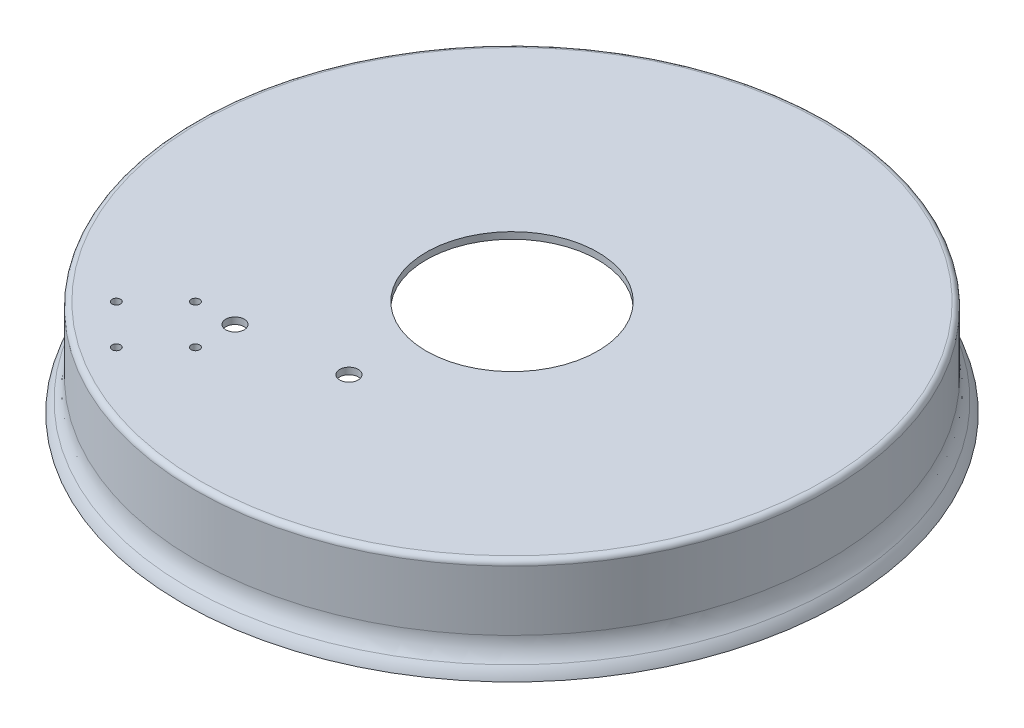
SolidWorks part; units mm, degrees
ref_plane "Front Plane" through (0, 0, 0) normal (0, 0, 1) x (1, 0, 0)
ref_plane "Top Plane" through (0, 0, 0) normal (0, 1, 0) x (1, 0, 0)
ref_plane "Right Plane" through (0, 0, 0) normal (1, 0, 0) x (0, 0, -1)
sketch "Sketch1" plane through (0, 0, 0) normal (0, 1, 0) x (1, 0, 0)
  circle A0 centre (0, 0) radius 120
  circle A1 centre (0, 0) radius 118
  dimension "D1" = 240
  dimension "D2" = 236
extrude "Boss-Extrude1" add sketch "Sketch1" along normal blind 32
sketch "Sketch2" plane through (0, 32, 0) normal (0, 1, 0) x (1, 0, 0)
  circle A0 centre (0, 0) radius 120
  circle A1 centre (0, 0) radius 32.5
  dimension "D1" = 65
  dimension "D2" = 240
extrude "Boss-Extrude2" add sketch "Sketch2" along normal blind 2.5
sketch "Sketch3" plane through (0, 34.5, 0) normal (0, 1, 0) x (1, 0, 0)
  circle A0 centre (-75, -75) radius 1.6
  circle A1 centre (-60, -60) radius 1.6
  circle A2 centre (-45, -75) radius 1.6
  circle A3 centre (-60, -90) radius 1.6
  dimension "D1" = 3.2
  dimension "D2" = 3.2
  dimension "D3" = 3.2
  dimension "D4" = 3.2
  dimension "D5" = 30
  dimension "D6" = 30
  dimension "D7" = 15
  dimension "D8" = 15
  dimension "D9" = 60
  dimension "D10" = 60
extrude "Cut-Extrude1" cut sketch "Sketch3" against normal up to surface (2.5 mm away) up to face at (0, 32, 32.5)
sketch "Sketch4" plane through (0, 34.5, 0) normal (0, 1, 0) x (1, 0, 0)
  circle A0 centre (-45, -60) radius 3.5
  circle A1 centre (-60, -60) radius 1.6 construction
  circle A2 centre (-45, -75) radius 1.6 construction
  dimension "D1" = 7
  dimension "D2" = 15
  dimension "D3" = 15
extrude "Cut-Extrude2" cut sketch "Sketch4" against normal up to surface (2.5 mm away) up to face at (-75, 32, 76.6)
fillet "Fillet1" radius 2 1 edges at (0, 34.5, 120)
sketch "Sketch5" plane through (0, 0, 0) normal (0, -1, 0) x (1, 0, 0)
  circle A0 centre (0, 0) radius 118
  circle A1 centre (0, 0) radius 125
  dimension "D1" = 250
  dimension "D2" = 236
extrude "Boss-Extrude3" add sketch "Sketch5" along normal blind 2
fillet "Fillet2" radius 12 1 edges at (0, 0, 120)
fillet "Fillet3" radius 12 1 edges at (0, 0, -125)
sketch "Sketch6" plane through (0, 34.5, 0) normal (0, 1, 0) x (1, 0, 0)
  circle A0 centre (-6.9162, -54.8774) radius 3.5
  point P2 (-6.9162, -54.8774)
  dimension "D1" = 7
extrude "Cut-Extrude3" cut sketch "Sketch6" against normal blind 26
